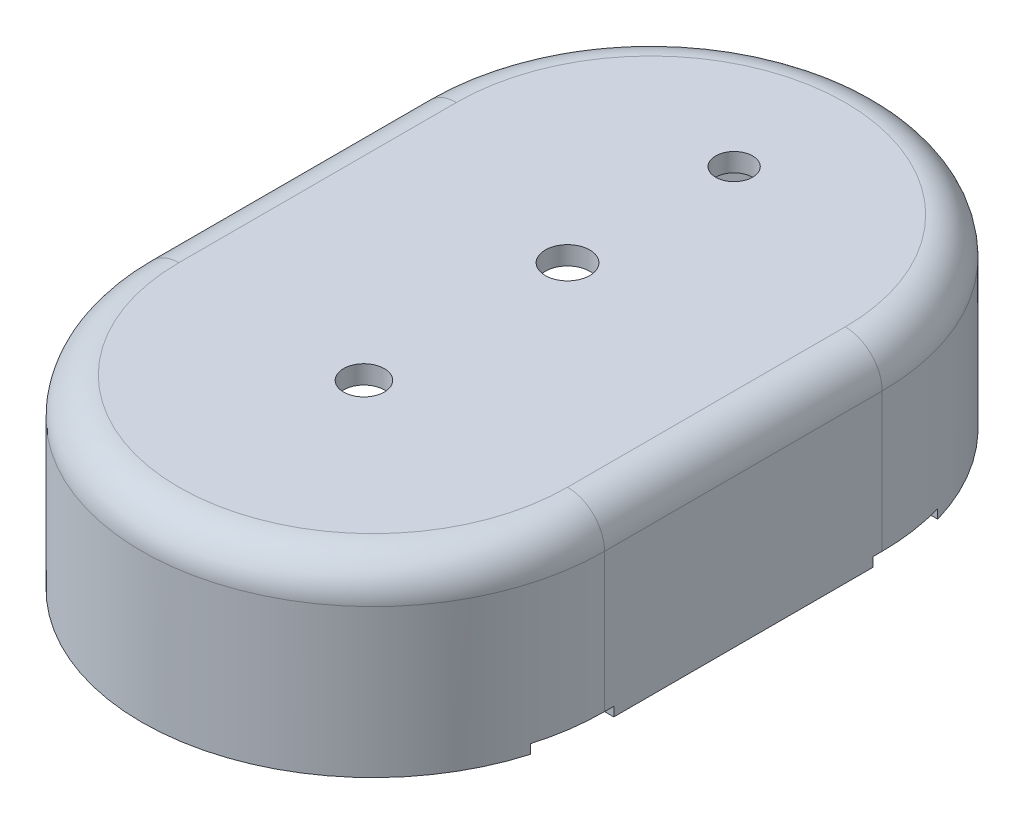
SolidWorks part; units mm, degrees
other "Markup1"
sketch "Sketch13" plane through (-62.5, 0, 100) normal (-0.211, -0.9674, 0.1404) x (-0.9699, 0.2251, 0.0932)
ref_plane "Front Plane" through (0, 0, 0) normal (0, 0, 1) x (1, 0, 0)
ref_plane "Top Plane" through (0, 0, 0) normal (0, 1, 0) x (1, 0, 0)
ref_plane "Right Plane" through (0, 0, 0) normal (1, 0, 0) x (0, 0, -1)
sketch "Sketch3" plane through (0, 0, 0) normal (0, 1, 0) x (1, 0, 0)
  line L0 (0, 100) -> (0, -100) construction
  line L2 (-62.5, -37.5) -> (-62.5, 37.5)
  line L4 (62.5, -37.5) -> (62.5, 37.5)
  line L8 (0, 0) -> (-62.5, 0) construction
  arc A1 (62.5, 37.5) -> (-62.5, 37.5) centre (0, 37.5) ccw
  arc A2 (62.5, -37.5) -> (-62.5, -37.5) centre (0, -37.5) cw
  point P0 (0, 0)
  dimension "D3" = 62.5
  dimension "D1" = 125
  dimension "D2" = 100
  dimension "D4" = 200
  dimension "D5" = 37.5
  dimension "D6" = 62.5
  dimension "D7" = 100
extrude "Boss-Extrude1" add sketch "Sketch3" along normal blind 50
fillet "Fillet1" radius 10 4 edges at (62.5, 50, 0) (0, 50, 100) (-62.5, 50, 0) (0, 50, -100)
shell "Shell1" thickness 5 removed face at (0, 0, 0)
sketch "Sketch4" plane through (0, 0, 0) normal (0, -1, 0) x (1, 0, 0)
  line L0 (57.5, 37.5) -> (57.5, -37.5) construction
  line L1 (-57.5, 37.5) -> (-57.5, -37.5) construction
  line L2 (57.5, 37.5) -> (57.5, -37.5) construction
  line L3 (-57.5, 37.5) -> (-57.5, -37.5) construction
  line L4 (-60.2, 37.5) -> (-60.2, -37.5)
  line L5 (60.2, 37.5) -> (60.2, -37.5)
  arc A0 (-57.5, -37.5) -> (57.5, -37.5) centre (0, -37.5) ccw construction
  arc A1 (57.5, 37.5) -> (-57.5, 37.5) centre (0, 37.5) ccw construction
  arc A2 (-57.5, -37.5) -> (57.5, -37.5) centre (0, -37.5) ccw construction
  arc A3 (57.5, 37.5) -> (-57.5, 37.5) centre (0, 37.5) ccw construction
  arc A4 (60.2, 37.5) -> (-60.2, 37.5) centre (0, 37.5) ccw
  arc A5 (-60.2, -37.5) -> (60.2, -37.5) centre (0, -37.5) ccw
  dimension "D1" = 2.7
extrude "Cut-Extrude2" cut sketch "Sketch4" against normal blind 2.5
sketch "Sketch5" plane through (-62.5, 0, 0) normal (-1, 0, 0) x (0, 0, 1)
  line L0 (0, 0) -> (0, 40) construction
  line L1 (0, 2.5) -> (-100, 2.5) construction
  line L2 (0, 0) -> (0, 2.5) construction
  line L3 (37.5, 40) -> (-37.5, 40) construction
  line L4 (55, 0) -> (55, 2.5)
  line L5 (55, 0) -> (35, 0)
  line L6 (-45, 2.5) -> (-45, 0) construction
  line L7 (-37.5, 0) -> (37.5, 0) construction
  line L8 (-55, 0) -> (-55, 2.5)
  line L9 (-55, 0) -> (-35, 0)
  line L11 (-55, 2.5) -> (-35, 2.5)
  line L12 (-35, 0) -> (-35, 2.5)
  line L17 (-100, 40) -> (-100, 0) construction
  line L18 (35, 0) -> (35, 2.5)
  line L19 (55, 2.5) -> (35, 2.5)
  dimension "D1" = 35
  dimension "D2" = 100
  dimension "D3" = 20
  dimension "D4" = 2.5
  dimension "D5" = 2.5
extrude "Cut-Extrude3" cut sketch "Sketch5" against normal through all
sketch "Sketch6" plane through (0, 50, 0) normal (0, 1, 0) x (1, 0, 0)
  line L0 (0, 90) -> (0, -90) construction
  arc A0 (52.5, 37.5) -> (-52.5, 37.5) centre (0, 37.5) ccw construction
  arc A1 (-52.5, -37.5) -> (52.5, -37.5) centre (0, -37.5) ccw construction
  circle A2 centre (0, 60) radius 5
  circle A3 centre (0, 15) radius 6
  circle A4 centre (0, -40) radius 5.5
  dimension "D1" = 10
  dimension "D3" = 12
  dimension "D6" = 11
  dimension "D2" = 30
  dimension "D4" = 75
  dimension "D5" = 50
extrude "Cut-Extrude4" cut sketch "Sketch6" against normal up to next
sketch "Sketch8" plane through (0, 2.5, 0) normal (0, -1, 0) x (1, 0, 0)
  line L0 (0, 95) -> (0, -90) construction
  line L1 (0, 0) -> (57.5, 0) construction
  line L3 (-5, 94.7822) -> (-5, 85.7822)
  line L4 (-1, 81.7822) -> (1, 81.7822)
  line L5 (5, 94.7822) -> (5, 85.7822)
  line L6 (0.6126, 93.3807) -> (5, 81.7822) construction
  line L7 (-5, 81.7822) -> (-0.6126, 93.3807) construction
  line L8 (57.5, -37.5) -> (57.5, 37.5) construction
  line L9 (5, -94.7822) -> (5, -85.7822)
  line L10 (-1, -81.7822) -> (1, -81.7822)
  line L11 (-5, -94.7822) -> (-5, -85.7822)
  line L17 (57.5, 37.5) -> (-57.5, 37.5) construction
  line L18 (57.5, -37.5) -> (57.5, 0)
  line L19 (57.5, 32.5) -> (48.5, 32.5)
  line L21 (57.2822, 42.5) -> (48.5, 42.5)
  line L22 (44.5, 36.5) -> (44.5, 38.5)
  line L23 (57.5, 37.5) -> (44.5, 42.5) construction
  line L24 (57.5, 37.5) -> (44.5, 32.5) construction
  line L25 (57.5, 32.5) -> (57.5, 37.5)
  line L26 (57.5, -32.5) -> (57.5, -37.5)
  line L27 (57.5, -32.5) -> (48.5, -32.5)
  line L28 (44.5, -36.5) -> (44.5, -38.5)
  line L29 (57.2822, -42.5) -> (48.5, -42.5)
  line L30 (-57.5, 32.5) -> (-57.5, 37.5)
  line L31 (-57.5, 32.5) -> (-48.5, 32.5)
  line L32 (-44.5, 36.5) -> (-44.5, 38.5)
  line L33 (-57.2822, 42.5) -> (-48.5, 42.5)
  line L34 (-57.5, -32.5) -> (-48.5, -32.5)
  line L35 (-44.5, -36.5) -> (-44.5, -38.5)
  line L36 (-57.2822, -42.5) -> (-48.5, -42.5)
  line L37 (-57.5, -32.5) -> (-57.5, -37.5)
  arc A0 (57.5, 37.5) -> (-57.5, 37.5) centre (0, 37.5) ccw construction
  arc A1 (-52.5, -37.5) -> (52.5, -37.5) centre (0, -37.5) ccw construction
  arc A2 (5, 94.7822) -> (-5, 94.7822) centre (0, 37.5) ccw
  arc A3 (5, 85.7822) -> (1, 81.7822) centre (1, 85.7822) cw
  arc A4 (-1, 81.7822) -> (-5, 85.7822) centre (-1, 85.7822) cw
  arc A5 (5, -85.7822) -> (1, -81.7822) centre (1, -85.7822) ccw
  arc A6 (-1, -81.7822) -> (-5, -85.7822) centre (-1, -85.7822) ccw
  arc A7 (5, -94.7822) -> (-5, -94.7822) centre (0, -37.5) cw
  arc A8 (57.5, 37.5) -> (-57.5, 37.5) centre (0, 37.5) ccw construction
  arc A9 (57.5, 37.5) -> (57.2822, 42.5) centre (0, 37.5) ccw
  arc A10 (5, 94.7822) -> (-57.5, 37.5) centre (0, 37.5) ccw
  arc A11 (48.5, 32.5) -> (44.5, 36.5) centre (48.5, 36.5) cw
  arc A12 (44.5, 38.5) -> (48.5, 42.5) centre (48.5, 38.5) cw
  arc A13 (48.5, -32.5) -> (44.5, -36.5) centre (48.5, -36.5) ccw
  arc A14 (44.5, -38.5) -> (48.5, -42.5) centre (48.5, -38.5) ccw
  arc A15 (57.5, -37.5) -> (57.2822, -42.5) centre (0, -37.5) cw
  arc A16 (-48.5, 32.5) -> (-44.5, 36.5) centre (-48.5, 36.5) ccw
  arc A17 (-44.5, 38.5) -> (-48.5, 42.5) centre (-48.5, 38.5) ccw
  arc A18 (-57.5, 37.5) -> (-57.2822, 42.5) centre (0, 37.5) cw
  arc A19 (-48.5, -32.5) -> (-44.5, -36.5) centre (-48.5, -36.5) cw
  arc A20 (-44.5, -38.5) -> (-48.5, -42.5) centre (-48.5, -38.5) cw
  arc A21 (-57.5, -37.5) -> (-57.2822, -42.5) centre (0, -37.5) ccw
  arc M10 (-57.5, 37.5) -> (57.5, 37.5) centre (0, 37.5) cw
  line M11 (57.5, 37.5) -> (57.5, -37.5)
  arc M12 (57.5, -37.5) -> (-57.5, -37.5) centre (0, -37.5) cw
  line M13 (-57.5, -37.5) -> (-57.5, 37.5)
  dimension "D3" = 4
  dimension "D8" = 4
  dimension "D1" = 10
  dimension "D2" = 13
  dimension "D4" = 9
  dimension "D5" = 10
  dimension "D6" = 13
  dimension "D7" = 12.7822
extrude "Boss-Extrude3" add sketch "Sketch8" against normal up to next contours A4 L4 A3 L5 L3 M10 | A12 L22 A11 L19 L21 M11 M10 | L28 A14 L29 L18 L27 A13 M12 | L10 A6 L11 L9 A5 M12 | A20 L35 A19 L34 L36 M13 M12 | L33 A17 L32 A16 L31 L30 A18 region at (0, 2.5, 88.668) region at (51.2946, 2.5, 37.4889) region at (-51.2946, 2.5, -37.4889) region at (51.2946, 2.5, -37.4889) region at (0, 2.5, -88.668)
fillet "Fillet3" radius 4 54 edges at (57.5, 21.25, 32.5) (56.0355, 43.5355, 32.5) (50.5, 45, 32.5) (45.6716, 45, 33.6716) (44.5, 45, 37.5) (45.6716, 45, 41.3284) (50.3807, 45, 42.5) (56.3416, 42.9141, 42.5) (57.2822, 21.25, -42.5) (56.3416, 42.9141, -42.5) (50.3807, 45, -42.5) (45.6716, 45, -41.3284) (44.5, 45, -37.5) (45.6716, 45, -33.6716) (50.5, 45, -32.5) (56.0355, 43.5355, -32.5) (5, 21.25, -94.7822) (5, 36.1473, -86.5589) (5, 45, -87.7718) (3.8284, 45, -82.9538) (0, 45, -81.7822) (-3.8284, 45, -82.9538) (-5, 45, -87.7718) (-5, 36.1473, -86.5589) (-57.5, 21.25, -32.5) (-56.0355, 43.5355, -32.5) (-50.5, 45, -32.5) (-45.6716, 45, -33.6716) (-44.5, 45, -37.5) (-45.6716, 45, -41.3284) (-50.3807, 45, -42.5) (-49.051, 36.1538, -42.5) (-57.2822, 21.25, 42.5) (-49.051, 36.1538, 42.5) (-50.3807, 45, 42.5) (-45.6716, 45, 41.3284) (-44.5, 45, 37.5) (-45.6716, 45, 33.6716) (-50.5, 45, 32.5) (-56.0355, 43.5355, 32.5) (5, 21.25, 94.7822) (5, 43.0451, 93.744) (5, 45, 87.7718) (3.8284, 45, 82.9538) (0, 45, 81.7822) (-3.8284, 45, 82.9538) (-5, 45, 87.7718) (-5, 43.0451, 93.744) (57.2822, 21.25, 42.5) (57.5, 21.25, -32.5) (-5, 21.25, -94.7822) (-57.2822, 21.25, -42.5) (-57.5, 21.25, 32.5) (-5, 21.25, 94.7822)
sketch "Sketch10" plane through (0, 45, 0) normal (0, -1, 0) x (1, 0, 0)
  line L0 (0, -15) -> (13, -15) construction
  line L1 (0, -15) -> (0, -2) construction
  line L2 (0, -2) -> (0, 2) construction
  line L6 (2.5, 1.8152) -> (2.5, -2.2426)
  line L7 (-2.5, 1.8152) -> (-2.5, -2.2426)
  line L8 (13, -15) -> (17, -15) construction
  line L9 (2.5, -31.8152) -> (2.5, -27.7574)
  line L10 (16.8152, -12.5) -> (12.7574, -12.5)
  line L11 (16.8152, -17.5) -> (12.7574, -17.5)
  line L12 (-2.5, -31.8152) -> (-2.5, -27.7574)
  line L13 (-16.8152, -12.5) -> (-12.7574, -12.5)
  line L14 (-16.8152, -17.5) -> (-12.7574, -17.5)
  circle A0 centre (0, -15) radius 6 construction
  circle A1 centre (0, -15) radius 6 construction
  arc A2 (12.7574, -17.5) -> (12.7574, -12.5) centre (0, -15) ccw
  arc A3 (16.8152, -17.5) -> (16.8152, -12.5) centre (0, -15) ccw
  arc A4 (2.5, -2.2426) -> (-2.5, -2.2426) centre (0, -15) ccw
  arc A5 (2.5, 1.8152) -> (-2.5, 1.8152) centre (0, -15) ccw
  arc A6 (2.5, -31.8152) -> (-2.5, -31.8152) centre (0, -15) cw
  arc A7 (2.5, -27.7574) -> (-2.5, -27.7574) centre (0, -15) cw
  arc A8 (-16.8152, -17.5) -> (-16.8152, -12.5) centre (0, -15) cw
  arc A9 (-12.7574, -17.5) -> (-12.7574, -12.5) centre (0, -15) cw
  point P12 (0, 2)
  point P18 (17, -15)
  dimension "D1" = 13
  dimension "D2" = 13
  dimension "D3" = 4
  dimension "D4" = 5
  dimension "D5" = 5
  dimension "D6" = 2.5
  dimension "D7" = 2.5
extrude "Boss-Extrude4" add sketch "Sketch10" along normal blind 4
sketch "Sketch12" plane through (0, 41, 0) normal (0, -1, 0) x (1, 0, 0)
  line L0 (0, -15) -> (0, -21) construction
  line L1 (0, -15) -> (6, -15) construction
  line L2 (-16.8152, -17.5) -> (-12.7574, -17.5)
  line L3 (-12.7574, -12.5) -> (-16.8152, -12.5)
  line L4 (-16.8152, -17.5) -> (-5.4544, -17.5)
  line L5 (-5.4544, -12.5) -> (-16.8152, -12.5)
  line L6 (16.8152, -17.5) -> (5.4544, -17.5)
  line L7 (5.4544, -12.5) -> (16.8152, -12.5)
  line L8 (2.5, -20.4544) -> (2.5, -31.8152)
  line L9 (-2.5, -31.8152) -> (-2.5, -20.4544)
  line L10 (2.5, -2.2426) -> (2.5, 1.8152)
  line L11 (-2.5, 1.8152) -> (-2.5, -2.2426)
  line L12 (2.5, -9.5456) -> (2.5, 1.8152)
  line L13 (-2.5, 1.8152) -> (-2.5, -9.5456)
  arc A0 (-5.4544, -17.5) -> (-2.5, -20.4544) centre (0, -15) ccw
  circle A1 centre (0, -15) radius 3
  arc A2 (16.8152, -12.5) -> (16.8152, -17.5) centre (0, -15) cw
  arc A3 (2.5, -31.8152) -> (-2.5, -31.8152) centre (0, -15) cw
  arc A4 (-16.8152, -12.5) -> (-16.8152, -17.5) centre (0, -15) ccw
  arc A5 (-12.7574, -12.5) -> (-12.7574, -17.5) centre (0, -15) ccw
  arc A6 (-16.8152, -12.5) -> (-16.8152, -17.5) centre (0, -15) ccw
  arc A8 (-2.5, -9.5456) -> (-5.4544, -12.5) centre (0, -15) ccw
  arc A9 (2.5, -2.2426) -> (-2.5, -2.2426) centre (0, -15) ccw
  arc A10 (2.5, 1.8152) -> (-2.5, 1.8152) centre (0, -15) ccw
  arc A12 (2.5, 1.8152) -> (-2.5, 1.8152) centre (0, -15) ccw
  arc A13 (5.4544, -12.5) -> (2.5, -9.5456) centre (0, -15) ccw
  arc A14 (2.5, -20.4544) -> (5.4544, -17.5) centre (0, -15) ccw
  dimension "D1" = 6
  dimension "D2" = 12
  dimension "D3" = 0
  dimension "D4" = 0
extrude "Boss-Extrude5" add sketch "Sketch12" along normal blind 3
fillet "Fillet4" radius 3 8 edges at (-2.5, 39.5, -20.4544) (-5.4544, 39.5, -17.5) (-5.4544, 39.5, -12.5) (-2.5, 39.5, -9.5456) (5.4544, 39.5, -17.5) (2.5, 39.5, -20.4544) (2.5, 39.5, -9.5456) (5.4544, 39.5, -12.5)
sketch "Sketch14" plane through (0, 2.5, 0) normal (0, -1, 0) x (1, 0, 0)
  line L0 (0, 81.7822) -> (0, 97.7) construction
  line L1 (-1, 81.7822) -> (1, 81.7822) construction
  line L2 (0, 0) -> (62.5, 0) construction
  line L5 (62.5, 35) -> (62.5, -35) construction
  line L6 (0, 0) -> (0, -97.7) construction
  line L7 (44.5, 37.5) -> (62.5, 37.5) construction
  line L8 (44.5, 38.5) -> (44.5, 36.5) construction
  line L9 (0, 86.5822) -> (0, 100) construction
  arc A0 (57.6003, 55) -> (-57.6003, 55) centre (0, 37.5) ccw construction
  circle A2 centre (0, 86.5822) radius 2.1
  arc A3 (-57.6003, -55) -> (57.6003, -55) centre (0, -37.5) ccw construction
  circle A4 centre (49.3, 37.5) radius 2.1
  circle A5 centre (-49.3, 37.5) radius 2.1
  circle A6 centre (49.3, -37.5) radius 2.1
  circle A7 centre (0, -86.5822) radius 2.1
  circle A8 centre (-49.3, -37.5) radius 2.1
  arc A9 (60, 55) -> (-60, 55) centre (0, 37.5) ccw construction
  dimension "D1" = 4.2
  dimension "D2" = 4.2
  dimension "4.8" = 4.8
  dimension "D3" = 4.8
extrude "Cut-Extrude5" cut sketch "Sketch14" against normal blind 6.5
